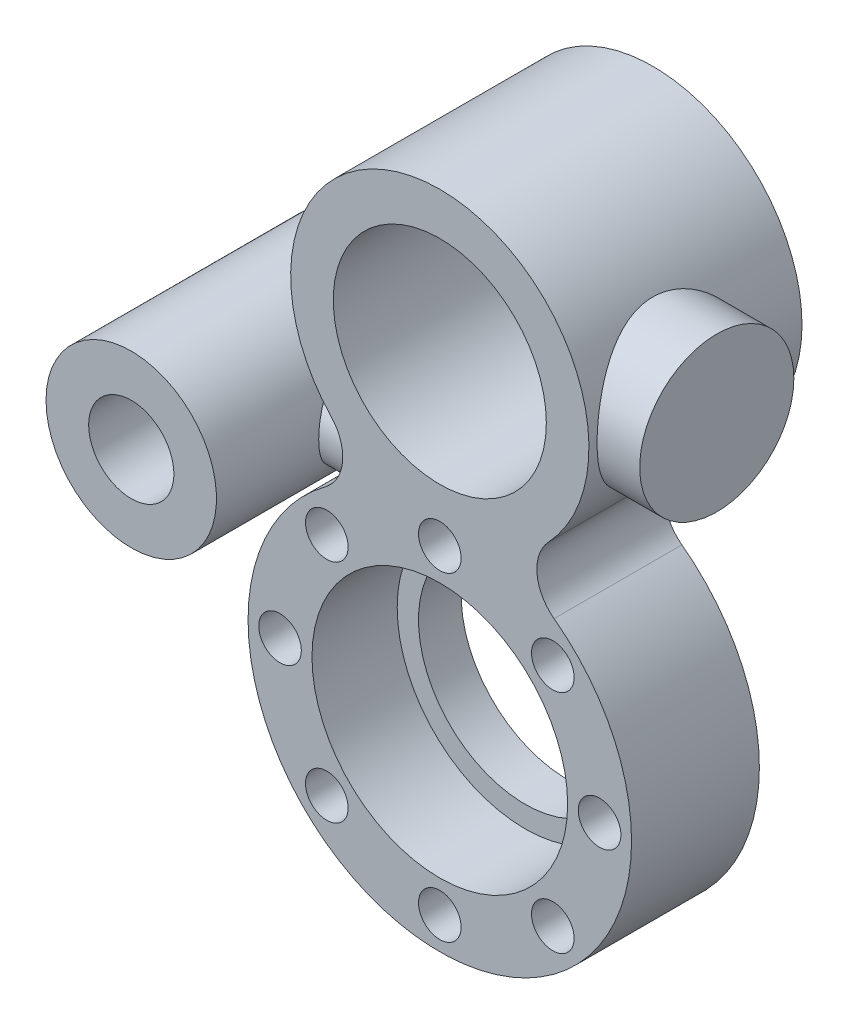
SolidWorks part; units mm, degrees
ref_plane "Front Plane" through (0, 0, 0) normal (0, 0, 1) x (1, 0, 0)
ref_plane "Top Plane" through (0, 0, 0) normal (0, 1, 0) x (1, 0, 0)
ref_plane "Right Plane" through (0, 0, 0) normal (1, 0, 0) x (0, 0, -1)
sketch "Sketch1" plane through (0, 0, 0) normal (0, 0, 1) x (1, 0, 0)
  line L1 (-35, 35) -> (35, 35) construction
  line L2 (-35, 35) -> (-25, 35)
  line L3 (25, 35) -> (35, 35)
  arc A1 (-35, 35) -> (35, 35) centre (0, 35) ccw
  arc A2 (-25, 35) -> (25, 35) centre (0, 35) ccw
  point P3 (0.932, 39.7859)
  point P7 (0, 0)
  dimension "D1" = 50
  dimension "D2" = 70
extrude "motor holder" add sketch "Sketch1" along normal blind 20 and the other way blind 30 contours A1 L3 A2 L2
mirror "Mirror1" about plane through (25, 35, -30) normal (0, -1, 0) of "motor holder"
sketch "Sketch10" plane through (0, 0, 0) normal (1, 0, 0) x (0, 0, -1)
  line L0 (-20, 5) -> (-20, -10)
  line L1 (-20, -10) -> (0, -10)
  line L2 (0, -10) -> (0, -15)
  line L3 (0, -15) -> (10, -15)
  line L4 (10, -15) -> (10, 5)
  line L5 (10, 5) -> (-20, 5)
  line L7 (-67.9189, -40) -> (23.1119, -40) construction
  line L9 (-20, 70) -> (-20, 0) construction
  dimension "D1" = 30
  dimension "D2" = 20
  dimension "D3" = 5
  dimension "D4" = 15
  dimension "D5" = 5
  dimension "D6" = 30
revolve "bearing holder" add sketch "Sketch10" angle 360 about L7
sketch "Sketch11" plane through (0, 0, 20) normal (0, 0, 1) x (1, 0, 0)
  circle A0 centre (0, -77.5) radius 5
  circle A1 centre (0, -40) radius 37.5 construction
  circle A5 centre (-26.5165, -66.5165) radius 5
  circle A6 centre (-37.5, -40) radius 5
  circle A7 centre (-26.5165, -13.4835) radius 5
  circle A8 centre (0, -2.5) radius 5
  circle A9 centre (26.5165, -13.4835) radius 5
  circle A10 centre (37.5, -40) radius 5
  circle A11 centre (26.5165, -66.5165) radius 5
  point P2 (0, -40)
  point P4 (0, 0)
  point P24 (0, -40)
  dimension "D1" = 10
  dimension "D2" = 75
  dimension "D3" = 8
extrude "screw holes" cut sketch "Sketch11" against normal through all
fillet "Fillet1" radius 10 2 edges at (-13.7951, 2.8333, 5) (13.7951, 2.8333, 5)
sketch "Sketch13" plane through (0, 0, 20) normal (0, 0, 1) x (1, 0, 0)
  circle A0 centre (0, -40) radius 45
  arc A1 (-26.8172, -3.8636) -> (26.8172, -3.8636) centre (0, -40) ccw construction
ref_plane "Plane1" through (35, 0, 0) normal (1, 0, 0) x (0, 0, -1)
sketch "Sketch14" plane through (35, 0, 0) normal (1, 0, 0) x (0, 0, -1)
  line L0 (-20, 35) -> (30, 35) construction
  line L1 (-20, 35) -> (10, 35) construction
  circle A0 centre (0, 35) radius 18.0903
extrude "Boss-Extrude4" add sketch "Sketch14" along normal blind 10 and the other way blind 10
ref_plane "Plane3" through (-35, 0, 0) normal (-1, 0, 0) x (0, 0, 1)
sketch "Sketch17" plane through (-35, 0, 0) normal (-1, 0, 0) x (0, 0, 1)
  circle A0 centre (5.0959, 0) radius 10
  point P2 (7.5915, 0)
  point P4 (5.0959, 0)
  dimension "D1" = 20
extrude "Boss-Extrude5" add sketch "Sketch17" against normal up to next and the other way blind 1
ref_plane "Plane4" through (0, 0, -4.9041) normal (0, 0, -1) x (-1, 0, 0)
sketch "Sketch18" plane through (0, 0, -4.9041) normal (0, 0, -1) x (-1, 0, 0)
  line L0 (36, 0) -> (26.8172, 0) construction
  circle A0 centre (53.3205, 0) radius 20
  circle A1 centre (53.3205, 0) radius 10
  dimension "D1" = 40
  dimension "D2" = 20
extrude "Boss-Extrude6" add sketch "Sketch18" along normal blind 10 and the other way blind 44
